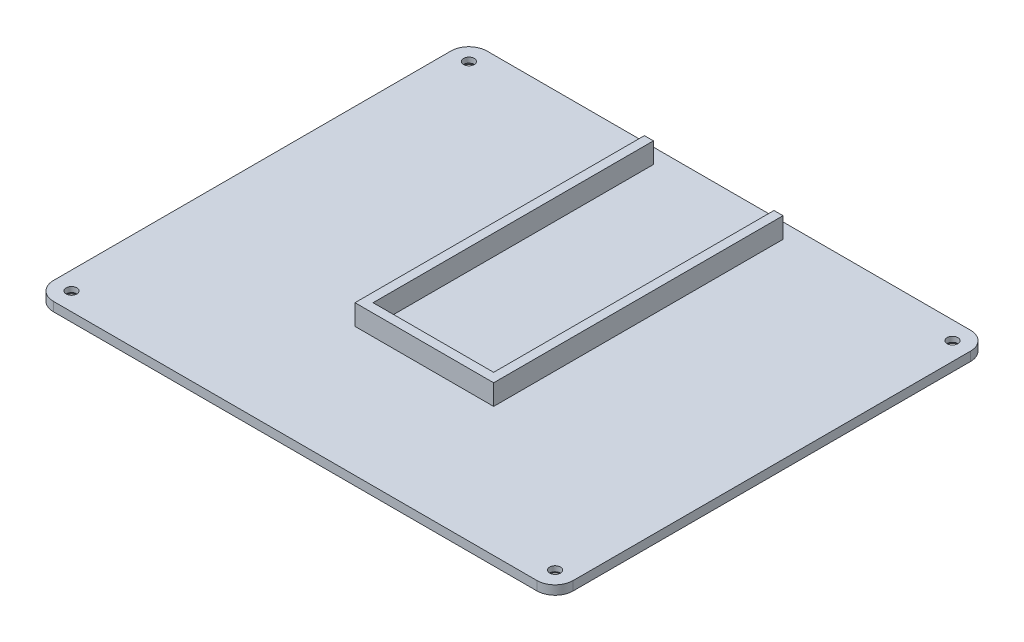
SolidWorks part; units mm, degrees
material "ABS"
ref_plane "Front" through (0, 0, 0) normal (0, 0, 1) x (1, 0, 0)
ref_plane "Top" through (0, 0, 0) normal (0, 1, 0) x (1, 0, 0)
ref_plane "Right" through (0, 0, 0) normal (1, 0, 0) x (0, 0, -1)
sketch "Sketch1" plane through (0, 0, 0) normal (0, 1, 0) x (1, 0, 0)
  line L1 (-43.1005, 35.9565) -> (43.1005, 35.9565)
  line L2 (-43.1005, 35.9565) -> (-43.1005, -35.9565)
  line L3 (-43.1005, -35.9565) -> (43.1005, -35.9565)
  line L4 (43.1005, 35.9565) -> (43.1005, -35.9565)
  line L5 (-43.1005, 35.9565) -> (43.1005, -35.9565) construction
  line L6 (-43.1005, -35.9565) -> (43.1005, 35.9565) construction
  point P0 (0, 0)
  dimension "D1" = 71.913
  dimension "D2" = 86.201
extrude "Boss-Extrude1" add sketch "Sketch1" along normal blind 1.5
fillet "Fillet1" radius 3 4 edges at (-43.1005, 0.75, 35.9565) (-43.1005, 0.75, -35.9565) (43.1005, 0.75, -35.9565) (43.1005, 0.75, 35.9565)
hole_wizard "#2-56 Tapped Hole1" positions "Sketch2" profile "Sketch4" tap size "#2-56" standard "ANSI Inch" end condition through all
sketch "Sketch2" plane through (0, 0, 0) normal (0, -1, 0) x (-1, 0, 0)
  point P0 (40.1005, -32.9565)
  point P3 (-40.1005, -32.9565)
  point P6 (-40.1005, 32.9565)
  point P9 (40.1005, 32.9565)
sketch "Sketch4" plane through (-40.1005, 0, 32.9565) normal (1, 0, 0) x (0, 0, -1)
  line L0 (0, 0) -> (0, 1.5)
  line L1 (0, 1.5) -> (0.889, 1.5)
  line L2 (0.889, 1.5) -> (0.889, 0.635)
  line L3 (0.889, 0.635) -> (1.524, 0)
  line L5 (1.524, 0) -> (0, 0)
  line L6 (-0.889, 0.635) -> (-1.524, 0) construction
  line L11 (0, -6.35) -> (0, 107.95) construction
  dimension "Thru Tap Drill Dia." = 1.778
  dimension "Thru Tap Drill Depth" = 1.5
  dimension "Near C'Sink Dia." = 3.048
  dimension "Near C'Sink Angle" = 90
cosmetic thread "Hole Thread1" parameters "D2"=2.1844
cosmetic thread "Hole Thread2" parameters "D2"=2.1844
cosmetic thread "Hole Thread3" parameters "D2"=2.1844
cosmetic thread "Hole Thread4" parameters "D2"=2.1844
sketch "Sketch5" plane through (0, 1.5, 0) normal (0, 1, 0) x (1, 0, 0)
  line L0 (-10, 35.9565) -> (-10, -13.0435)
  line L1 (40.1005, 35.9565) -> (-40.1005, 35.9565) construction
  line L2 (-10, -13.0435) -> (10, -13.0435)
  line L3 (10, -13.0435) -> (10, 35.9565)
  line L4 (10, 35.9565) -> (11.5, 35.9565)
  line L5 (11.5, 35.9565) -> (11.5, -14.5435)
  line L6 (11.5, -14.5435) -> (-11.5, -14.5435)
  line L7 (-11.5, -14.5435) -> (-11.5, 35.9565)
  line L8 (-11.5, 35.9565) -> (-10, 35.9565)
  line L9 (0, -13.0435) -> (0, 0) construction
  line L10 (-11.5, 33.4565) -> (-10, 33.4565)
  line L11 (10, 33.4565) -> (11.5, 33.4565)
  point P15 (0, 0)
  dimension "D1" = 49
  dimension "D2" = 1.5
  dimension "D3" = 1.5
  dimension "D4" = 20
  dimension "D5" = 2.5
extrude "Boss-Extrude2" add sketch "Sketch5" along normal blind 3.4 contours L11 L3 L2 L0 L10 L7 L6 L5 region at (-10.5323, 1.5, -10.2065)
